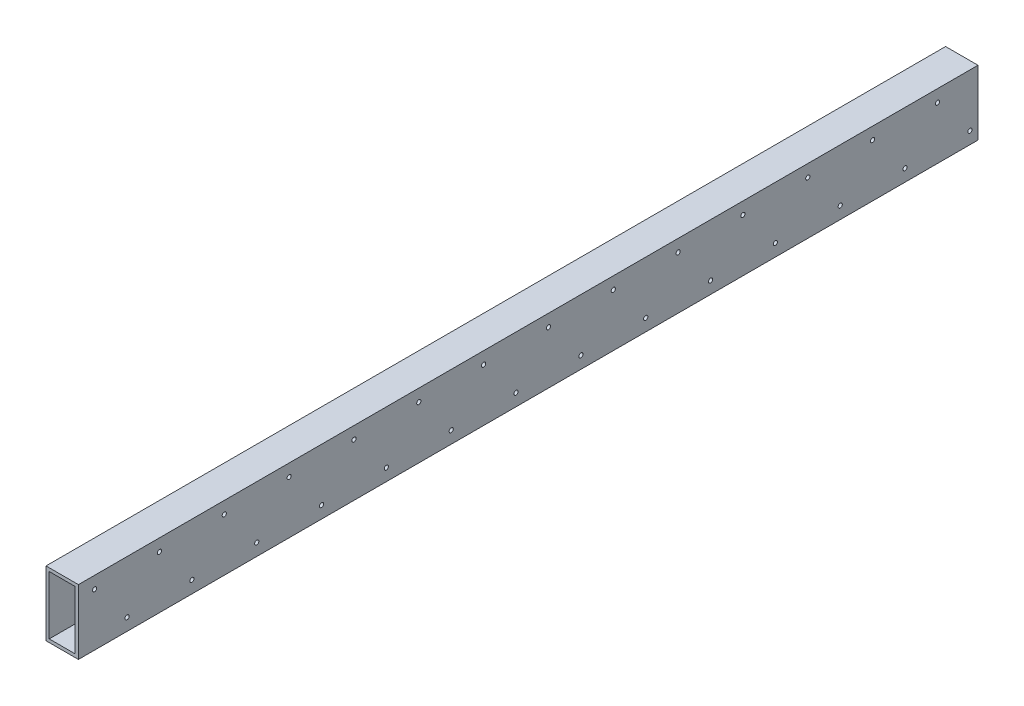
SolidWorks part; units mm, degrees
material "6061-T6 (SS)"
ref_plane "Front" through (0, 0, 0) normal (0, 0, 1) x (1, 0, 0)
ref_plane "Top" through (0, 0, 0) normal (0, 1, 0) x (1, 0, 0)
ref_plane "Right" through (0, 0, 0) normal (1, 0, 0) x (0, 0, -1)
sketch "Sketch1" plane through (0, 0, 0) normal (0, 0, 1) x (1, 0, 0)
  line L1 (-12.7, -25.4) -> (12.7, -25.4)
  line L2 (-12.7, -25.4) -> (-12.7, 25.4)
  line L3 (-12.7, 25.4) -> (12.7, 25.4)
  line L4 (12.7, -25.4) -> (12.7, 25.4)
  line L5 (-12.7, -25.4) -> (12.7, 25.4) construction
  line L6 (-12.7, 25.4) -> (12.7, -25.4) construction
  point P0 (0, 0)
  dimension "D1" = 50.8
  dimension "D2" = 25.4
extrude "Extrude-Thin1" add sketch "Sketch1" along normal blind 704.85 thin thin type one direction reverse wall 2.54
sketch "Sketch5" plane through (12.7, 0, 0) normal (1, 0, 0) x (0, 0, -1)
  line L0 (-704.85, -25.4) -> (0, -25.4) construction
  line L1 (0, -25.4) -> (0, 25.4) construction
  line L2 (-704.85, 25.4) -> (0, 25.4) construction
  point P98 (-6.35, -15.875)
  point P100 (-31.75, 15.875)
  point P112 (-57.15, -15.875)
  point P113 (-82.55, 15.875)
  point P114 (-107.95, -15.875)
  point P115 (-133.35, 15.875)
  point P116 (-158.75, -15.875)
  point P117 (-184.15, 15.875)
  point P118 (-209.55, -15.875)
  point P119 (-234.95, 15.875)
  point P120 (-260.35, -15.875)
  point P121 (-285.75, 15.875)
  point P122 (-311.15, -15.875)
  point P123 (-336.55, 15.875)
  point P124 (-361.95, -15.875)
  point P125 (-387.35, 15.875)
  point P126 (-412.75, -15.875)
  point P127 (-438.15, 15.875)
  point P128 (-463.55, -15.875)
  point P129 (-488.95, 15.875)
  point P130 (-514.35, -15.875)
  point P131 (-539.75, 15.875)
  point P132 (-565.15, -15.875)
  point P133 (-590.55, 15.875)
  point P134 (-615.95, -15.875)
  point P135 (-641.35, 15.875)
  point P136 (-666.75, -15.875)
  point P137 (-692.15, 15.875)
  point P138 (0, 0)
  dimension "D1" = 9.525
  dimension "D2" = 6.35
  dimension "D3" = 25.4
  dimension "D4" = 9.525
  dimension "D6" = 25.4
  dimension "D5" = 14
hole_wizard "1/8 (0.13) Diameter Hole1" positions "Sketch5" profile "Sketch4" hole size "1/8" standard "ANSI Inch" end condition up to next
sketch "Sketch4" plane through (12.7, -15.875, 6.35) normal (0, 1, 0) x (0, 0, -1)
  line L0 (0, 0) -> (0, 2.54)
  line L1 (0, 2.54) -> (1.651, 2.54)
  line L2 (1.651, 2.54) -> (1.651, 0)
  line L5 (1.651, 0) -> (0, 0)
  line L11 (0, -6.35) -> (0, 107.95) construction
  dimension "Thru Hole Dia." = 3.302
  dimension "Thru Hole Depth" = 2.54
